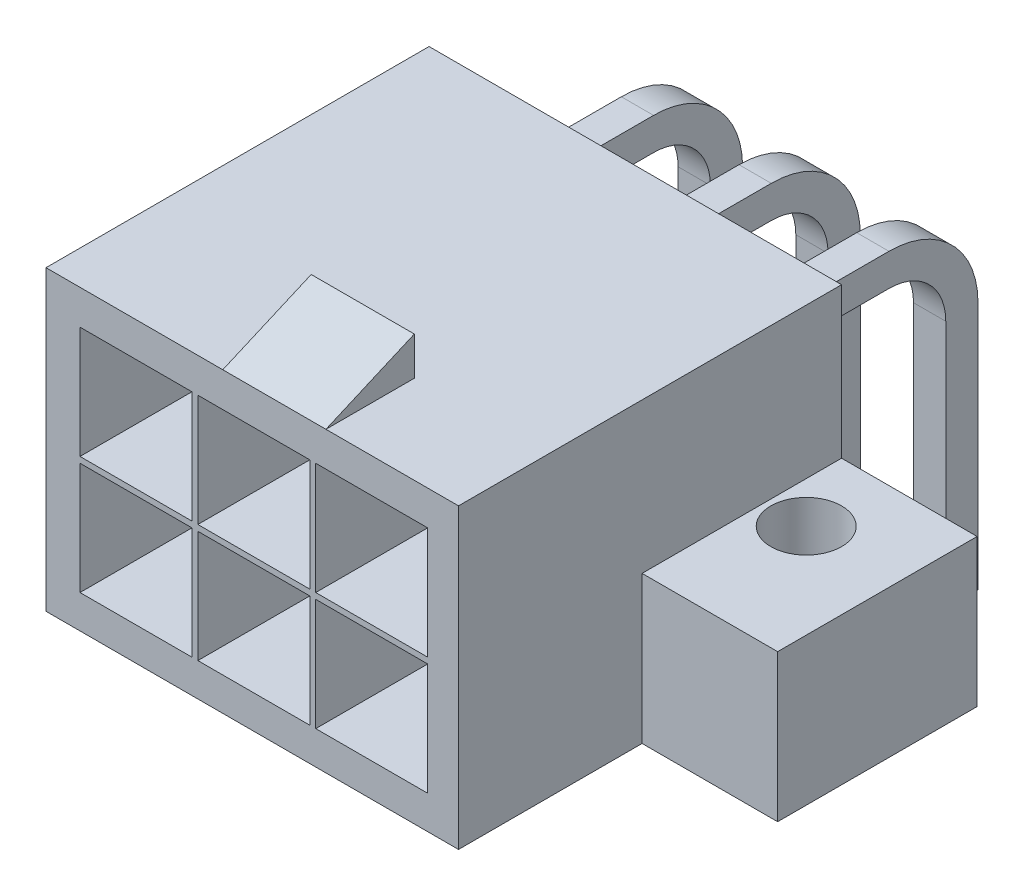
SolidWorks part; units mm, degrees
ref_plane "Front Plane" through (0, 0, 0) normal (0, 0, 1) x (1, 0, 0)
ref_plane "Top Plane" through (0, 0, 0) normal (0, 1, 0) x (1, 0, 0)
ref_plane "Right Plane" through (0, 0, 0) normal (1, 0, 0) x (0, 0, -1)
sketch "Sketch1" plane through (0, 0, 0) normal (0, 1, 0) x (1, 0, 0)
  line L1 (0, 0) -> (14, 0)
  line L2 (0, 0) -> (0, 13)
  line L3 (0, 13) -> (14, 13)
  line L4 (14, 0) -> (14, 13)
extrude "Boss-Extrude1" add sketch "Sketch1" along normal blind 10.1
sketch "Sketch2" plane through (0, 10.1, 0) normal (0, 1, 0) x (1, 0, 0)
  line L0 (0, 0) -> (14, 0) construction
  line L1 (6, 3) -> (9.5, 3)
  line L2 (6, 3) -> (6, 0)
  line L3 (6, 0) -> (9.5, 0)
  line L4 (9.5, 3) -> (9.5, 0)
extrude "Boss-Extrude2" add sketch "Sketch2" along normal blind 1.3
sketch "Sketch3" plane through (9.5, 0, 0) normal (1, 0, 0) x (0, 0, -1)
  line L0 (0, 10.1) -> (3, 11.4)
  line L1 (3, 11.4) -> (0, 11.4)
  line L2 (0, 11.4) -> (0, 10.1)
extrude "Cut-Extrude1" cut sketch "Sketch3" against normal up to next
sketch "Sketch4" plane through (14, 0, 0) normal (1, 0, 0) x (0, 0, -1)
  line L1 (13, 0) -> (6.23, 0)
  line L2 (13, 0) -> (13, 5)
  line L3 (13, 5) -> (6.23, 5)
  line L4 (6.23, 0) -> (6.23, 5)
extrude "Boss-Extrude3" add sketch "Sketch4" along normal blind 4.6
sketch "Sketch5" plane through (0, 0, 0) normal (-1, 0, 0) x (0, 0, 1)
  line L5 (-6.23, 5) -> (-13, 5)
  line L6 (-6.23, 5) -> (-6.23, 0)
  line L7 (-6.23, 0) -> (-13, 0)
  line L8 (-13, 5) -> (-13, 0)
extrude "Boss-Extrude4" add sketch "Sketch5" along normal blind 4.6
sketch "Sketch6" plane through (0, 0, 0) normal (0, 0, 1) x (1, 0, 0)
  line L1 (1.154, 8.9291) -> (12.954, 8.9291) construction
  line L2 (1.154, 8.9291) -> (1.154, 1.1291) construction
  line L3 (1.154, 1.1291) -> (12.954, 1.1291) construction
  line L4 (12.954, 8.9291) -> (12.954, 1.1291) construction
  line L12 (4.954, 5.1291) -> (5.154, 5.1291) construction
  line L13 (1.154, 8.9291) -> (4.954, 8.9291)
  line L14 (1.154, 8.9291) -> (1.154, 5.1291)
  line L15 (1.154, 5.1291) -> (4.954, 5.1291)
  line L16 (4.954, 8.9291) -> (4.954, 5.1291)
  line L17 (12.954, 1.1291) -> (9.154, 1.1291)
  line L18 (12.954, 1.1291) -> (12.954, 4.9291)
  line L19 (12.954, 4.9291) -> (9.154, 4.9291)
  line L20 (9.154, 1.1291) -> (9.154, 4.9291)
  line L21 (12.954, 8.9291) -> (9.154, 8.9291)
  line L22 (12.954, 8.9291) -> (12.954, 5.1291)
  line L23 (12.954, 5.1291) -> (9.154, 5.1291)
  line L24 (9.154, 8.9291) -> (9.154, 5.1291)
  line L25 (1.154, 1.1291) -> (4.954, 1.1291)
  line L26 (1.154, 1.1291) -> (1.154, 4.9291)
  line L27 (1.154, 4.9291) -> (4.954, 4.9291)
  line L28 (4.954, 1.1291) -> (4.954, 4.9291)
  line L30 (5.154, 5.1291) -> (8.954, 5.1291)
  line L31 (5.154, 5.1291) -> (5.154, 8.9291)
  line L32 (5.154, 8.9291) -> (8.954, 8.9291)
  line L33 (8.954, 5.1291) -> (8.954, 8.9291)
  line L34 (5.154, 4.9291) -> (8.954, 4.9291)
  line L35 (5.154, 4.9291) -> (5.154, 1.1291)
  line L36 (5.154, 1.1291) -> (8.954, 1.1291)
  line L37 (8.954, 4.9291) -> (8.954, 1.1291)
extrude "Cut-Extrude2" cut sketch "Sketch6" against normal blind 9.2
sketch "Sketch7" plane through (0, 0, -13) normal (0, 0, -1) x (-1, 0, 0)
  line L1 (-11.5829, 7.861) -> (-10.4886, 7.861)
  line L2 (-11.5829, 7.861) -> (-11.5829, 6.7666)
  line L3 (-11.5829, 6.7666) -> (-10.4886, 6.7666)
  line L4 (-10.4886, 7.861) -> (-10.4886, 6.7666)
  line L5 (-7.5886, 7.861) -> (-6.4943, 7.861)
  line L6 (-7.5886, 7.861) -> (-7.5886, 6.7666)
  line L7 (-7.5886, 6.7666) -> (-6.4943, 6.7666)
  line L8 (-6.4943, 7.861) -> (-6.4943, 6.7666)
  line L9 (-3.5943, 7.861) -> (-2.5, 7.861)
  line L10 (-3.5943, 7.861) -> (-3.5943, 6.7666)
  line L11 (-3.5943, 6.7666) -> (-2.5, 6.7666)
  line L12 (-2.5, 7.861) -> (-2.5, 6.7666)
  line L14 (-6.4943, 7.861) -> (-6.4943, 10.1) construction
  line L16 (-14, 10.1) -> (0, 10.1) construction
  line L17 (-10.4886, 6.7666) -> (-7.5886, 6.7666) construction
  line L18 (-6.4943, 6.7666) -> (-3.5943, 6.7666) construction
ref_plane "Plane1" through (4, 0, 0) normal (1, 0, 0) x (0, 0, -1)
sketch "Sketch9" plane through (4, 0, 0) normal (1, 0, 0) x (0, 0, -1)
  line L1 (13, 0) -> (14, 0)
  line L2 (14, 0) -> (19.5, 0)
sketch "Sketch8" plane through (4, 0, 0) normal (1, 0, 0) x (0, 0, -1)
  line L0 (13, 7.3138) -> (17.0253, 7.3138)
  line L1 (13, 7.861) -> (13, 6.7666) construction
  line L2 (19.5, 4.8391) -> (19.5, 0)
  line L3 (19.5, 4.8391) -> (17.0253, 4.8391) construction
  line L4 (17.0253, 4.8391) -> (17.0253, 7.3138) construction
  line L5 (19.5, 0) -> (19.5, -3.6)
  arc A0 (17.0253, 7.3138) -> (19.5, 4.8391) centre (17.0253, 4.8391) cw
extrude "Boss-Extrude5" add sketch "Sketch7" against normal blind 10
sweep "Sweep2" add profiles "Sketch7<4>" path "Sketch8"
sketch "Sketch7<4>" plane through (0, 0, -13) normal (0, 0, -1) x (-1, 0, 0) same geometry as "Sketch7"
sketch "Sketch10" plane through (0, 0, -13) normal (0, 0, -1) x (-1, 0, 0)
  line L1 (-2.5171, 3.3369) -> (-3.6114, 3.3369)
  line L2 (-2.5171, 3.3369) -> (-2.5171, 2.2469)
  line L3 (-2.5171, 2.2469) -> (-3.6114, 2.2469)
  line L4 (-3.6114, 3.3369) -> (-3.6114, 2.2469)
  line L5 (-11.5829, 6.7666) -> (-11.5829, 0) construction
  line L6 (-6.5114, 3.3366) -> (-7.5886, 3.3366)
  line L7 (-6.5114, 3.3366) -> (-6.5114, 2.2423)
  line L8 (-6.5114, 2.2423) -> (-7.5886, 2.2423)
  line L9 (-7.5886, 3.3366) -> (-7.5886, 2.2423)
  line L10 (-10.4886, 3.3366) -> (-11.5786, 3.3366)
  line L11 (-10.4886, 3.3366) -> (-10.4886, 2.2423)
  line L12 (-10.4886, 2.2423) -> (-11.5786, 2.2423)
  line L13 (-11.5786, 3.3366) -> (-11.5786, 2.2423)
  line L14 (-18.6, 0) -> (4.6, 0) construction
  line L15 (-10.4886, 6.7666) -> (-10.4886, 3.3366) construction
  line L16 (-11.5786, 2.2423) -> (-0.8383, 2.2423) construction
  line L17 (-10.4886, 2.7895) -> (-7.5886, 2.7895) construction
  line L18 (-6.5114, 2.7895) -> (-3.6114, 2.7919) construction
sketch "Sketch11" plane through (4, 0, 0) normal (1, 0, 0) x (0, 0, -1)
  line L0 (13, 2.7919) -> (14, 1.7919) construction
  line L1 (13, 3.3369) -> (13, 2.2469) construction
  line L2 (14, 1.7919) -> (14, 0) construction
  line L3 (14, 0) -> (14, -3.6) construction
  line L4 (14, 1.7919) -> (14, 0)
  line L5 (14, 0) -> (14, -3.6)
  line L6 (13, 6.7666) -> (13, 0) construction
  arc A0 (13, 2.7919) -> (14, 1.7919) centre (13, 1.7919) cw
sweep "Sweep3" add profiles "Sketch10" path "Sketch11"
extrude "Boss-Extrude6" add sketch "Sketch10<2>" against normal blind 10
sketch "Sketch10<2>" plane through (0, 0, -13) normal (0, 0, -1) x (-1, 0, 0) same geometry as "Sketch10"
sketch "Sketch12" plane through (0, 0, 0) normal (0, -1, 0) x (1, 0, 0)
  line L0 (-4.6, -10.4) -> (-1.4, -10.4) construction
  line L3 (-4.6, -13) -> (-4.6, -6.23) construction
  line L4 (-1.4, -10.4) -> (15.4, -10.4) construction
  line L5 (15.4, -10.4) -> (18.6, -10.4) construction
  line L6 (18.6, -6.23) -> (18.6, -13) construction
  circle A0 centre (-1.4, -10.4) radius 1.2
  circle A1 centre (15.4, -10.4) radius 1.2
extrude "Cut-Extrude3" cut sketch "Sketch12" against normal through all
ref_plane "Plane2" through (-5.4739, 0, -5.4955) normal (0.7057, 0, 0.7085) x (0.7085, 0, -0.7057)
ref_plane "Plane3" through (8.526, 0, -8.5597) normal (0.7057, 0, -0.7085) x (-0.7085, 0, -0.7057)
ref_axis "pin1" through (3.0642, -8.1657, -14) along (0, 1, 0)
